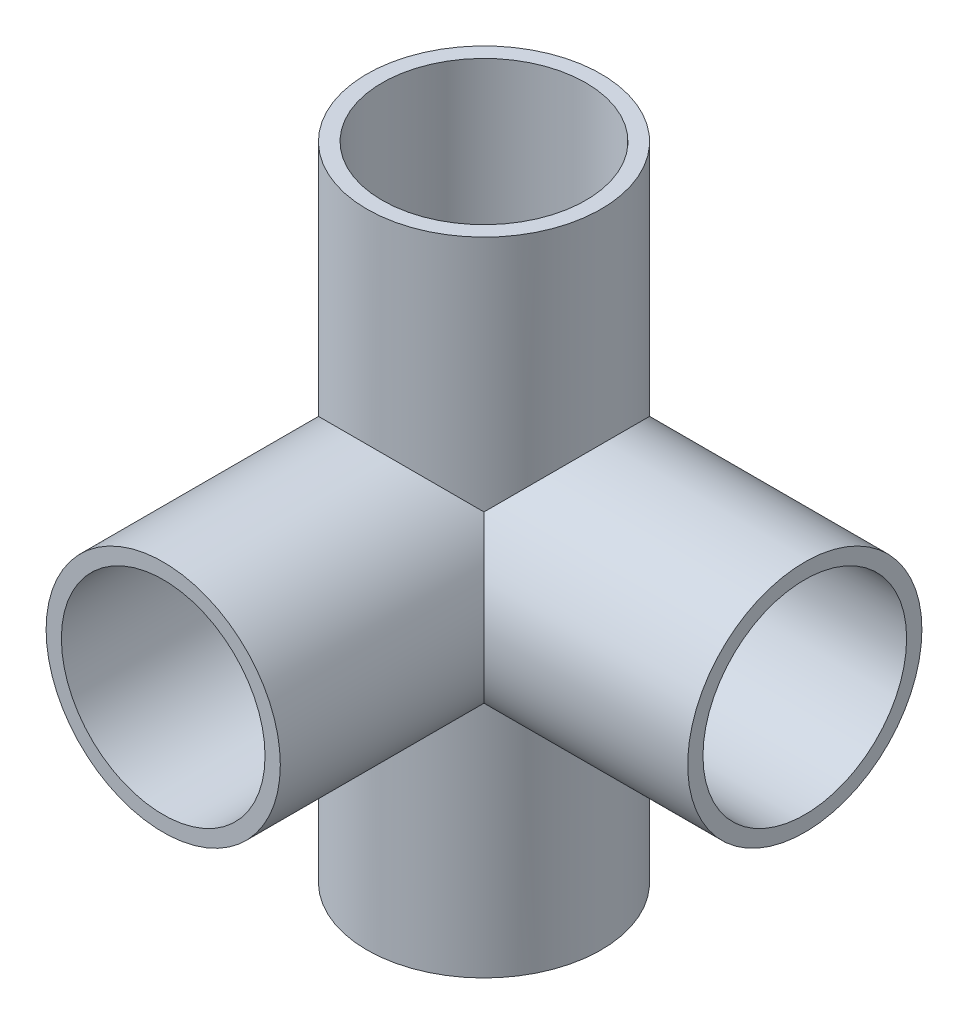
SolidWorks part; units mm, degrees
ref_plane "Front Plane" through (0, 0, 0) normal (0, 0, 1) x (1, 0, 0)
ref_plane "Top Plane" through (0, 0, 0) normal (0, 1, 0) x (1, 0, 0)
ref_plane "Right Plane" through (0, 0, 0) normal (1, 0, 0) x (0, 0, -1)
sketch "Sketch3" plane through (0, 0, 0) normal (0, 1, 0) x (1, 0, 0)
  circle A0 centre (0, 0) radius 12.7
  circle A1 centre (0, 0) radius 14.605
  dimension "D1" = 25.4
  dimension "D2" = 29.21
extrude "Boss-Extrude2" add sketch "Sketch3" along normal blind 80.01
sketch "Sketch4" plane through (0, 0, 0) normal (0, 0, 1) x (1, 0, 0)
  line L0 (0, 0) -> (0, 40.005) construction
  circle A0 centre (0, 40.005) radius 14.605
  dimension "D2" = 29.21
  dimension "D1" = 40.005
extrude "Boss-Extrude3" add sketch "Sketch4" along normal blind 40.005
sketch "Sketch5" plane through (0, 0, 40.005) normal (0, 0, 1) x (1, 0, 0)
  circle A0 centre (0, 40.005) radius 12.7
  circle A1 centre (0, 40.005) radius 14.605 construction
  dimension "D1" = 25.4
extrude "Cut-Extrude1" cut sketch "Sketch5" against normal up to surface (40.005 mm away) up to face at (0, 40.005, 0)
sketch "Sketch6" plane through (0, 0, 0) normal (1, 0, 0) x (0, 0, -1)
  line L0 (0, 0) -> (0, 40.005) construction
  circle A0 centre (0, 40.005) radius 14.605
  dimension "D2" = 29.21
  dimension "D1" = 40.005
extrude "Boss-Extrude4" add sketch "Sketch6" along normal blind 40.005
sketch "Sketch7" plane through (40.005, 0, 0) normal (1, 0, 0) x (0, 0, -1)
  circle A0 centre (0, 40.005) radius 12.7
  circle A1 centre (0, 40.005) radius 14.605 construction
  dimension "D1" = 25.4
extrude "Cut-Extrude2" cut sketch "Sketch7" against normal blind 40.005
sketch "Sketch8" plane through (0, 80.01, 0) normal (0, 1, 0) x (1, 0, 0)
  circle A0 centre (0, 0) radius 12.7
extrude "Cut-Extrude3" cut sketch "Sketch8" against normal through all
sketch "Sketch9" plane through (0, 0, 40.005) normal (0, 0, 1) x (1, 0, 0)
  circle A0 centre (0, 40.005) radius 12.7
extrude "Cut-Extrude4" cut sketch "Sketch9" against normal up to surface (40.005 mm away) up to face at (2.4002, 40.0291, 9.1001)
